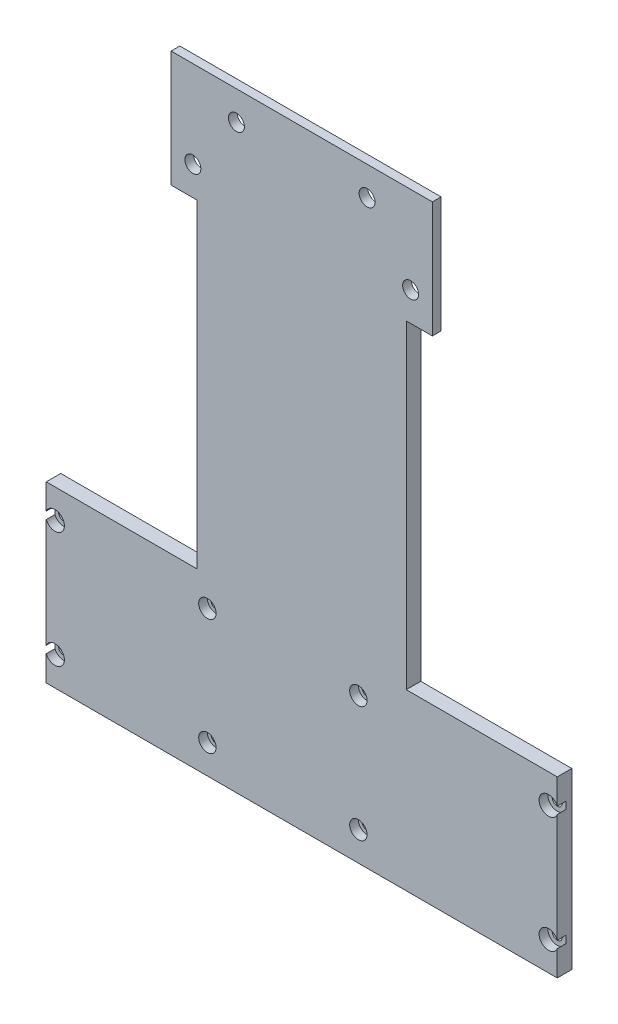
SolidWorks part; units mm, degrees
ref_plane "正面" through (0, 0, 0) normal (0, 0, 1) x (1, 0, 0)
ref_plane "平面" through (0, 0, 0) normal (0, 1, 0) x (1, 0, 0)
ref_plane "右側面" through (0, 0, 0) normal (1, 0, 0) x (0, 0, -1)
sketch "ｽｹｯﾁ1" plane through (0, 0, 0) normal (0, 0, 1) x (1, 0, 0)
  line L0 (-45, -20) -> (-36, -20)
  line L2 (-45, -20) -> (-45, 20)
  line L3 (-45, 20) -> (45, 20)
  line L4 (45, -20) -> (45, 20)
  line L5 (-45, -20) -> (45, 20) construction
  line L6 (-45, 20) -> (45, -20) construction
  line L7 (-36, -20) -> (-36, -190)
  line L8 (-36, -190) -> (36, -190)
  line L9 (36, -190) -> (36, -20)
  line L10 (36, -20) -> (45, -20)
  point P0 (0, 0)
  dimension "D1" = 40
  dimension "D2" = 90
  dimension "D3" = 9
  dimension "D4" = 72
  dimension "D5" = 170
extrude "ﾎﾞｽ - 押し出し1" add sketch "ｽｹｯﾁ1" along normal blind 3
sketch "ｽｹｯﾁ2" plane through (0, 0, 0) normal (0, 0, -1) x (-1, 0, 0)
  line L1 (-36, -20) -> (36, -20)
  line L2 (-36, -20) -> (-36, -190)
  line L3 (-36, -190) -> (36, -190)
  line L4 (36, -20) -> (36, -190)
extrude "ﾎﾞｽ - 押し出し2" add sketch "ｽｹｯﾁ2" along normal blind 2
sketch "ｽｹｯﾁ4" plane through (0, 0, 0) normal (0, 0, -1) x (-1, 0, 0)
  line L0 (-45, -20) -> (-45, 20) construction
  line L1 (45, 20) -> (45, -20) construction
  line L2 (-45, 20) -> (45, 20) construction
  line L3 (-36, -20) -> (-45, -20) construction
  line L4 (45, -20) -> (36, -20) construction
  circle A0 centre (-22.5, 10) radius 2.75
  circle A1 centre (22.5, 10) radius 2.75
  circle A2 centre (37.5, -10) radius 2.75
  circle A3 centre (-37.5, -10) radius 2.75
  dimension "D1" = 5.5
  dimension "D2" = 5.5
  dimension "D3" = 5.5
  dimension "D4" = 5.5
  dimension "D5" = 25
  dimension "D6" = 7.5
  dimension "D7" = 45
  dimension "D8" = 7.5
  dimension "D9" = 10
  dimension "D10" = 10
  dimension "D11" = 10
  dimension "D12" = 10
extrude "ｶｯﾄ - 押し出し1" cut sketch "ｽｹｯﾁ4" against normal through all
sketch "ｽｹｯﾁ7" plane through (0, 0, 3) normal (0, 0, 1) x (1, 0, 0)
  line L1 (36, -190) -> (88, -190)
  line L2 (36, -190) -> (36, -130)
  line L3 (36, -130) -> (88, -130)
  line L4 (88, -190) -> (88, -130)
  dimension "D1" = 52
  dimension "D2" = 60
extrude "ﾎﾞｽ - 押し出し3" add sketch "ｽｹｯﾁ7" against normal up to surface (5 mm away) up to face at (0, -105, -2)
sketch "ｽｹｯﾁ8" plane through (0, 0, 3) normal (0, 0, 1) x (1, 0, 0)
  line L0 (-36, -190) -> (88, -190) construction
  line L1 (88, -190) -> (88, -130) construction
  circle A0 centre (85, -140) radius 1.75
  circle A1 centre (85, -180) radius 1.75
  dimension "D1" = 3.5
  dimension "D2" = 3.5
  dimension "D3" = 10
  dimension "D4" = 40
  dimension "D5" = 3
  dimension "D6" = 3
extrude "ｶｯﾄ - 押し出し2" cut sketch "ｽｹｯﾁ8" against normal through all
sketch "ｽｹｯﾁ9" plane through (0, 0, 3) normal (0, 0, 1) x (1, 0, 0)
  circle A0 centre (85, -140) radius 3.25
  circle A1 centre (85, -180) radius 3.25
  dimension "D1" = 6.5
  dimension "D2" = 6.5
extrude "ｶｯﾄ - 押し出し3" cut sketch "ｽｹｯﾁ9" against normal blind 3
mirror "ﾐﾗｰ1" about plane through (0, 0, 0) normal (1, 0, 0) of "ｶｯﾄ - 押し出し1", "ｶｯﾄ - 押し出し2", "ｶｯﾄ - 押し出し3", "ﾎﾞｽ - 押し出し3", "ﾎﾞｽ - 押し出し1"
ref_axis "軸1" through (0, -200.5, 0) along (0, 1, 0)
sketch "ｽｹｯﾁ10" plane through (0, 0, 3) normal (0, 0, 1) x (1, 0, 0)
  line L0 (88, -130) -> (36, -130) construction
  line L1 (-88, -130) -> (-36, -130) construction
  line L2 (0, -200.5) -> (0, 30.5) construction
  circle A0 centre (19.5, -140) radius 1.75
  circle A1 centre (19.5, -180) radius 1.75
  circle A2 centre (-32.5, -180) radius 1.75
  circle A3 centre (-32.5, -140) radius 1.75
  dimension "D1" = 3.5
  dimension "D2" = 3.5
  dimension "D3" = 3.5
  dimension "D4" = 3.5
  dimension "D5" = 40
  dimension "D6" = 10
  dimension "D7" = 10
  dimension "D8" = 40
  dimension "D9" = 52
  dimension "D10" = 52
  dimension "D11" = 32.5
  dimension "D12" = 32.5
extrude "ｶｯﾄ - 押し出し4" cut sketch "ｽｹｯﾁ10" against normal through all
sketch "ｽｹｯﾁ11" plane through (0, 0, 3) normal (0, 0, 1) x (1, 0, 0)
  circle A0 centre (-32.5, -140) radius 3
  circle A1 centre (19.5, -140) radius 3
  circle A2 centre (19.5, -180) radius 3
  circle A3 centre (-32.5, -180) radius 3
  dimension "D1" = 6
  dimension "D2" = 6
  dimension "D3" = 6
  dimension "D4" = 6
extrude "ｶｯﾄ - 押し出し5" cut sketch "ｽｹｯﾁ11" against normal blind 3
